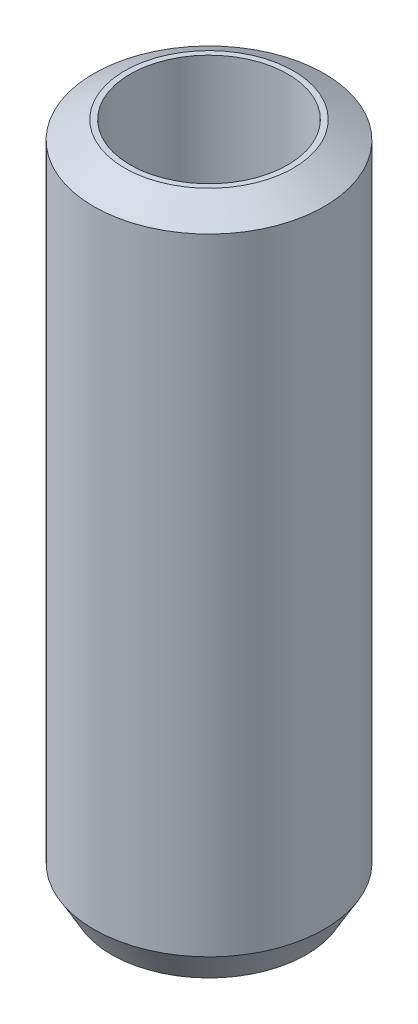
SolidWorks part; units mm, degrees
ref_plane "Front Plane" through (0, 0, 0) normal (0, 0, 1) x (1, 0, 0)
ref_plane "Top Plane" through (0, 0, 0) normal (0, 1, 0) x (1, 0, 0)
ref_plane "Right Plane" through (0, 0, 0) normal (1, 0, 0) x (0, 0, -1)
sketch "Sketch1" plane through (0, 0, 0) normal (0, 1, 0) x (1, 0, 0)
  circle A0 centre (0, 0) radius 10
  dimension "SHAFT_OD" = 20
extrude "Boss-Extrude1" add sketch "Sketch1" along normal blind 58.5579
sketch "Sketch2" plane through (0, 0, 0) normal (0, 1, 0) x (1, 0, 0)
  circle A0 centre (0, 0) radius 6.8382
  dimension "BORE_D" = 13.6764
extrude "Cut-Extrude1" cut sketch "Sketch2" along normal through all
chamfer "Chamfer1" distance 1.5471 angle 60 2 edges at (0, 58.5579, 10) (0, 0, 10) first distance on face at (0, 58.5579, 10) first distance on face at (0, 0, 6.8382)
